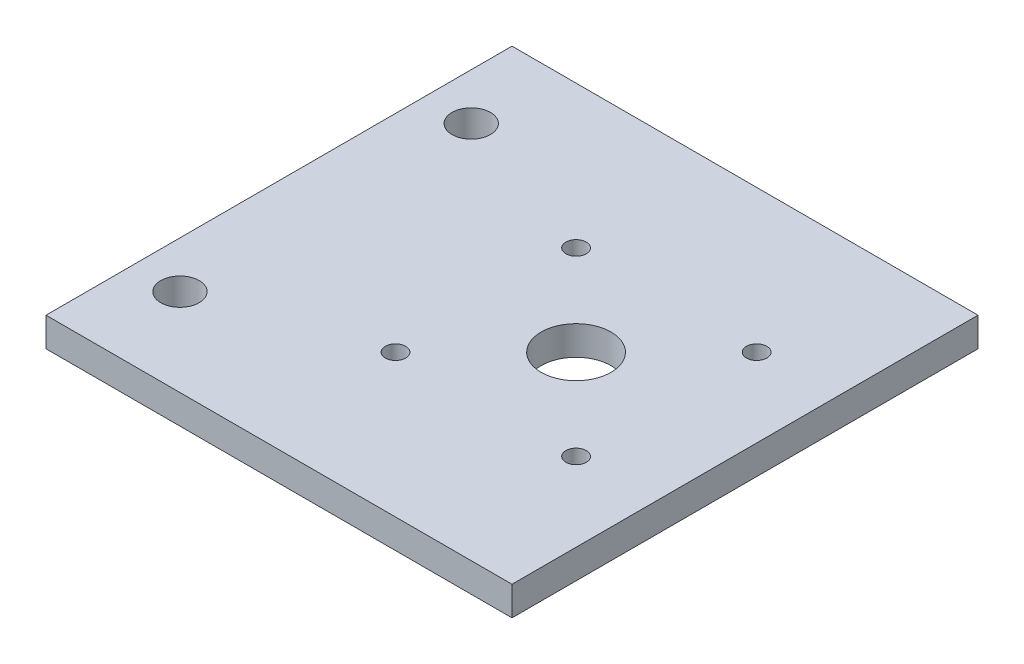
SolidWorks part; units mm, degrees
material "Lega 1060"
ref_plane "Piano frontale" through (0, 0, 0) normal (0, 0, 1) x (1, 0, 0)
ref_plane "Piano superiore" through (0, 0, 0) normal (0, 1, 0) x (1, 0, 0)
ref_plane "Piano destro" through (0, 0, 0) normal (1, 0, 0) x (0, 0, -1)
sketch "Schizzo1" plane through (0, 0, 0) normal (0, 0, 1) x (1, 0, 0)
  line L1 (0, 0) -> (80, 0)
  line L2 (0, 0) -> (0, 5)
  line L3 (0, 5) -> (80, 5)
  line L4 (80, 0) -> (80, 5)
  dimension "D1" = 5
  dimension "D2" = 80
extrude "Estrusione-Estrusione1" add sketch "Schizzo1" along normal blind 80
hole_wizard "Foro per Vite M6-1" positions "Schizzo3" profile "Schizzo2" hole size "M6" standard "ISO" end condition through all
sketch "Schizzo3" plane through (0, 5, 0) normal (0, 1, 0) x (1, 0, 0)
  line L0 (-9.8996, -40) -> (95.021, -40) construction
  line L2 (80, -80) -> (0, -80) construction
  line L3 (80, 0) -> (0, 0) construction
  line L4 (0, -80) -> (0, 0) construction
  point P0 (8, -15)
  point P1 (8, -65)
  dimension "D1" = 15
  dimension "D2" = 8
sketch "Schizzo2" plane through (8, 5, 15) normal (1, 0, 0) x (0, 0, 1)
  line L0 (0, 0) -> (0, 5)
  line L1 (0, 5) -> (3.3, 5)
  line L2 (3.3, 5) -> (3.3, 0)
  line L5 (3.3, 0) -> (0, 0)
  line L11 (0, -6.35) -> (0, 107.95) construction
  dimension "Thru Hole Dia." = 6.6
  dimension "Thru Hole Depth" = 5
sketch "Schizzo4" plane through (0, 5, 0) normal (0, 1, 0) x (1, 0, 0)
  line L0 (0, -80) -> (0, 0) construction
  line L3 (19.8289, -40) -> (54.8798, -40) construction
  line L4 (80, -80) -> (0, -80) construction
  line L5 (80, 0) -> (0, 0) construction
  circle A0 centre (51, -40) radius 6
  circle A1 centre (8, -15) radius 3.3 construction
  dimension "D1" = 12
  dimension "D2" = 43
extrude "Taglio-Estrusione1" cut sketch "Schizzo4" against normal through all
sketch "Schizzo6" plane through (0, 5, 0) normal (0, 1, 0) x (1, 0, 0)
  line L0 (42.0101, -40) -> (55.783, -40) construction
  line L1 (51, -40) -> (51, -30.1482) construction
  line L2 (80, -80) -> (0, -80) construction
  line L3 (80, 0) -> (0, 0) construction
  circle A0 centre (35.5, -24.5) radius 1.75
  circle A1 centre (66.5, -24.5) radius 1.75
  circle A2 centre (66.5, -55.5) radius 1.75
  circle A3 centre (35.5, -55.5) radius 1.75
  dimension "D1" = 3.5
  dimension "D2" = 31
  dimension "D3" = 31
  dimension "D4" = 15.5
extrude "Taglio-Estrusione3" cut sketch "Schizzo6" against normal through all
